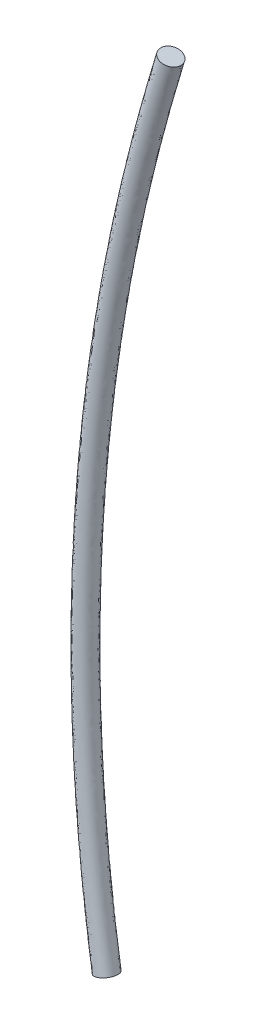
SolidWorks part; units mm, degrees
material "Custom Plastic"
ref_plane "X-Y Datum" through (0, 0, 0) normal (0, 0, 1) x (1, 0, 0)
ref_plane "X-Z Datum" through (0, 0, 0) normal (0, 1, 0) x (1, 0, 0)
ref_plane "Y-Z Datum" through (0, 0, 0) normal (1, 0, 0) x (0, 0, -1)
sketch3d "3DSketch2"
  circle A0 centre (-192.8639, 81.6813, 219.825) radius 4.5 construction
  spline S0 degree 2 poles (-192.8639, 81.6813, 219.825) (-228.1818, -42.4402, 223.9889) (-198.6168, -158.9053, 233.86) knots 0 0 0 0.949414 0.949414 0.949414
  point P1 (0, 0, 0)
  point P3 (0, 0, 0)
  point P8 (-194.403, 77.4526, 219.825)
  point P17 (-198.6168, -158.9053, 233.86)
sweep "Sweep2" add path "3DSketch2" circular profile diameter 6.35 parameters "D3"=6.35
